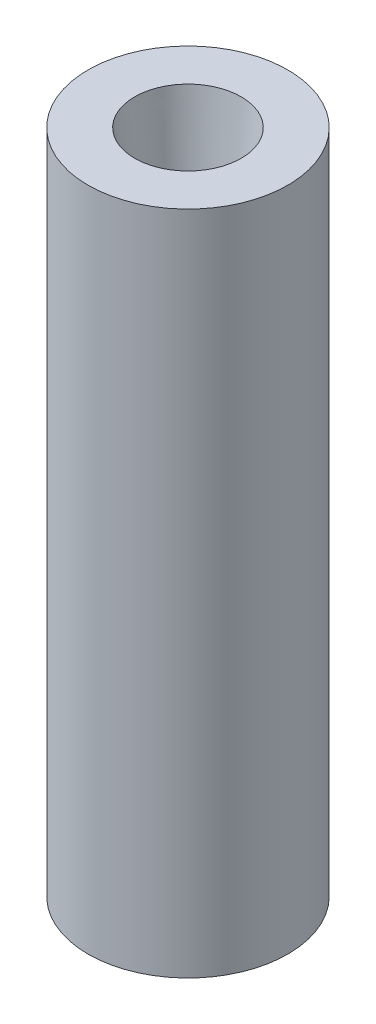
SolidWorks part; units mm, degrees
ref_plane "Front Plane" through (0, 0, 0) normal (0, 0, 1) x (1, 0, 0)
ref_plane "Top Plane" through (0, 0, 0) normal (0, 1, 0) x (1, 0, 0)
ref_plane "Right Plane" through (0, 0, 0) normal (1, 0, 0) x (0, 0, -1)
sketch "Sketch1" plane through (0, 0, 0) normal (0, 1, 0) x (1, 0, 0)
  circle A0 centre (0, 0) radius 7.5
  dimension "D1" = 15
extrude "Boss-Extrude1" add sketch "Sketch1" along normal blind 50
sketch "Sketch3" plane through (0, 0, 0) normal (0, -1, 0) x (1, 0, 0)
  line L1 (-1.725, 1.725) -> (1.725, 1.725)
  line L2 (-1.725, 1.725) -> (-1.725, -1.725)
  line L3 (-1.725, -1.725) -> (1.725, -1.725)
  line L4 (1.725, 1.725) -> (1.725, -1.725)
  line L5 (-1.725, 1.725) -> (1.725, -1.725) construction
  line L6 (-1.725, -1.725) -> (1.725, 1.725) construction
  point P0 (0, 0)
  dimension "D1" = 3.45
extrude "Cut-Extrude2" cut sketch "Sketch3" against normal blind 25
sketch "Sketch4" plane through (0, 50, 0) normal (0, 1, 0) x (1, 0, 0)
  circle A0 centre (0, 0) radius 4
  dimension "D1" = 8
ref_plane "Plane1" through (0, 25, 0) normal (0, 1, 0) x (1, 0, 0)
sketch "Sketch6" plane through (0, 25, 0) normal (0, 1, 0) x (1, 0, 0)
  circle A0 centre (0, 0) radius 1.5
  dimension "D1" = 3
loft "Cut-Loft2" cut profiles "Sketch6", "Sketch4" connector at (-1.4233, 25, -0.4734) connector at (-3.9712, 50, -0.4789)
